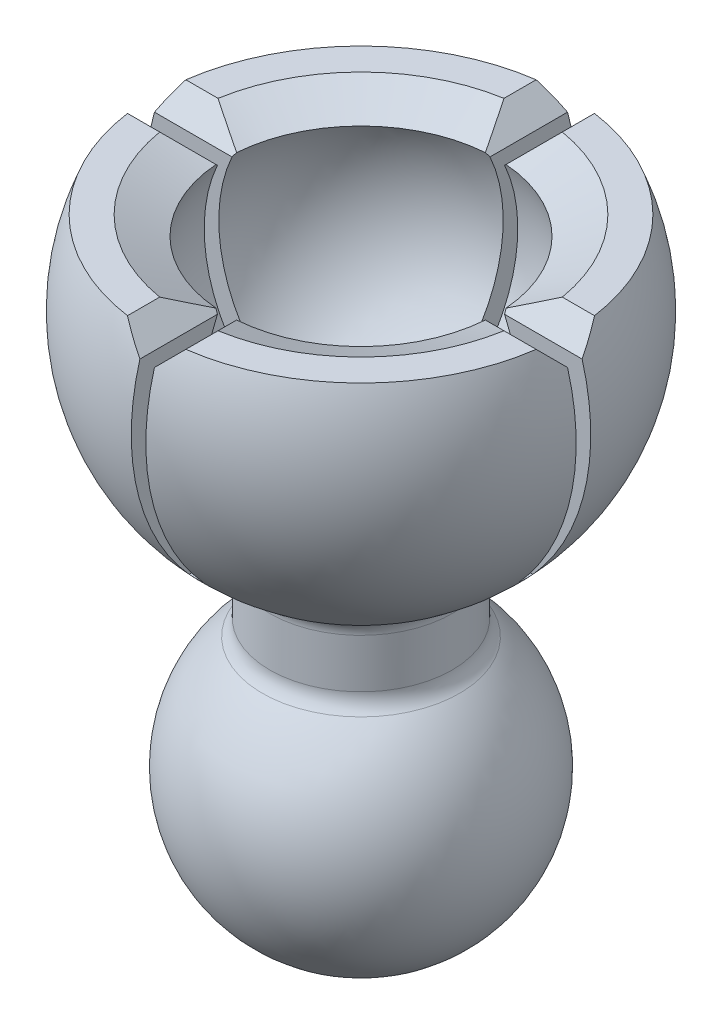
SolidWorks part; units mm, degrees
other "Camera1"
other "ExplView1" [suppressed]
ref_plane "Front Plane" through (0, 0, 0) normal (0, 0, 1) x (1, 0, 0)
ref_plane "Top Plane" through (0, 0, 0) normal (0, 1, 0) x (1, 0, 0)
ref_plane "Right Plane" through (0, 0, 0) normal (1, 0, 0) x (0, 0, -1)
sketch "Sketch1" plane through (0, 0, 0) normal (0, 0, 1) x (1, 0, 0)
  line L0 (0, 0) -> (0, 13.7515)
  line L1 (-3.175, 9.3512) -> (-3.175, 11.8912)
  line L2 (-6.0822, 21.8672) -> (-4.7066, 21.2111)
  line L3 (0, 0) -> (0, -5.6046) construction
  line L4 (-3.175, 23.1027) -> (-3.175, 25.6427) construction
  line L6 (3.175, 25.6427) -> (3.175, 23.1027) construction
  line L7 (-0.889, 13.8278) -> (-0.889, 0.0763) construction
  line L18 (-6.0822, 21.8672) -> (-7.1915, 21.8672)
  arc A0 (0, 0) -> (-3.175, 9.3512) centre (0, 5.2146) cw
  arc A2 (-4.7066, 21.2111) -> (0, 13.7515) centre (0, 18.9661) ccw
  arc A3 (-3.175, 23.1027) -> (3.175, 23.1027) centre (0, 18.9661) ccw construction
  arc A4 (-7.1915, 21.8672) -> (-3.175, 11.8912) centre (0, 18.9661) ccw
  arc A6 (3.175, 25.6427) -> (-3.175, 25.6427) centre (0, 32.7176) ccw construction
  point P1 (-5.2146, 18.9661)
  dimension "D2" = 5.2146
  dimension "D7" = 1.524
  dimension "D11" = 2.54
  dimension "D3" = 6.35
  dimension "D5" = 2.54
  dimension "D6" = 0.508
  dimension "D8" = 1.778
revolve "Revolve1 - main body" add sketch "Sketch1" angle 360 about L3
ref_plane "Plane1 - socket base plane" through (0, 13.7515, 0) normal (0, -1, 0) x (-1, 0, 0)
sketch "Sketch2" plane through (0, 13.7515, 0) normal (0, -1, 0) x (-1, 0, 0)
  line L0 (0, 0) -> (9.7315, 0) construction
  line L1 (0, 0.254) -> (9.7315, 0.254)
  line L2 (0, -0.254) -> (9.7315, -0.254)
  arc A0 (0, 0.254) -> (0, -0.254) centre (0, 0) ccw
  arc A1 (9.7315, -0.254) -> (9.7315, 0.254) centre (9.7315, 0) ccw
  point P3 (4.8658, 0)
  dimension "D1" = 0.508
  dimension "D2" = 2.54
extrude "Cut-Extrude1 - socket slit" cut sketch "Sketch2" against normal through all
ref_axis "Axis1" through (0, -7.824, 0) along (0, 1, 0)
pattern_circular "CirPattern1 - pattern slits" count 4 over 360 about axis through (0, -7.824, 0) along (0, 1, 0) of "Cut-Extrude1 - socket slit"
chamfer "Chamfer1" distance 0.762 8 edges at (6.6319, 21.8672, 0.254) (6.6319, 21.8672, -0.254) (0.254, 21.8672, -6.6319) (-0.254, 21.8672, -6.6319) (-0.254, 21.8672, 6.6319) (0.254, 21.8672, 6.6319) (-6.6319, 21.8672, -0.254) (-6.6319, 21.8672, 0.254)
fillet "Fillet1" radius 0.762 2 edges at (0, 11.8912, 3.175) (0, 9.3512, 3.175)
